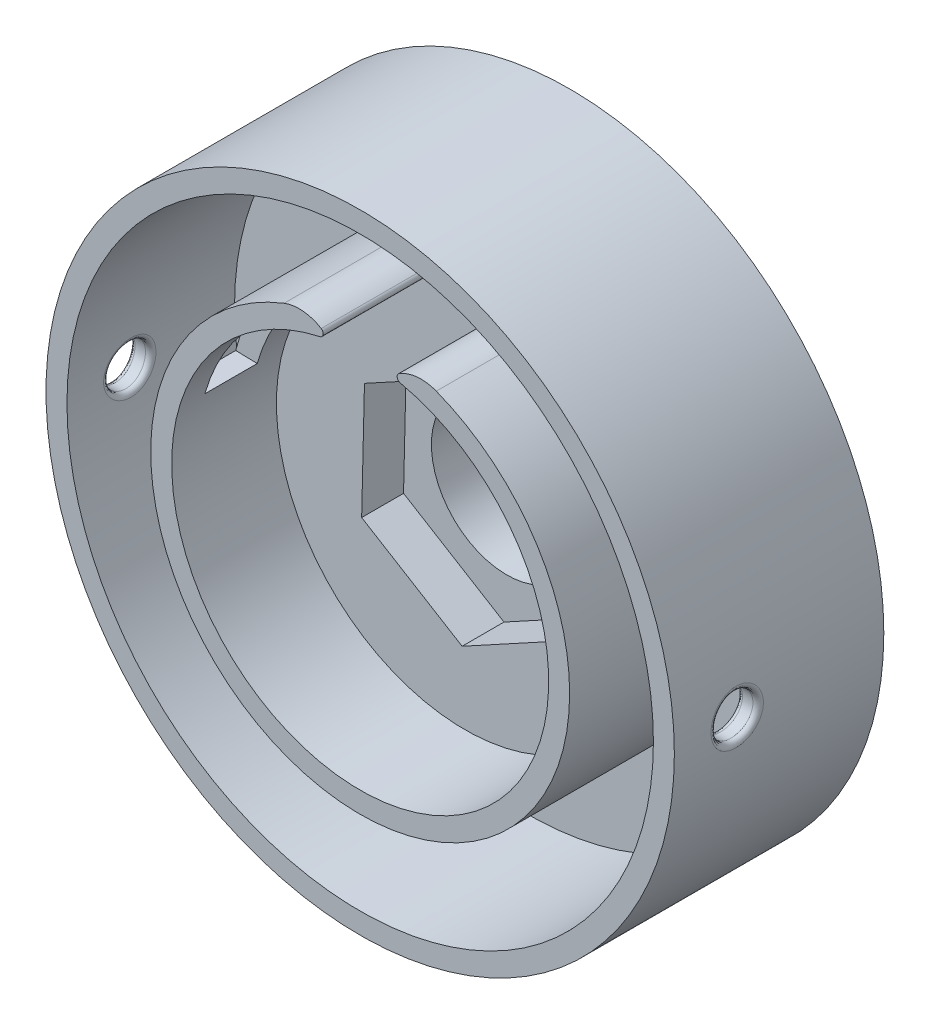
SolidWorks part; units mm, degrees
ref_plane "Front Plane" through (0, 0, 0) normal (0, 0, 1) x (1, 0, 0)
ref_plane "Top Plane" through (0, 0, 0) normal (0, 1, 0) x (1, 0, 0)
ref_plane "Right Plane" through (0, 0, 0) normal (1, 0, 0) x (0, 0, -1)
sketch "Sketch1" plane through (0, 0, 0) normal (0, 0, 1) x (1, 0, 0)
  circle A0 centre (0, 0) radius 15
extrude "Boss-Extrude1" add sketch "Sketch1" along normal blind 10
sketch "Sketch2" plane through (0, 0, 10) normal (0, 0, 1) x (1, 0, 0)
  circle A0 centre (0, 0) radius 3.6
extrude "Cut-Extrude1" cut sketch "Sketch2" against normal through all
sketch "Sketch3" plane through (0, 0, 10) normal (0, 0, 1) x (1, 0, 0)
  circle A0 centre (0, 0) radius 9
extrude "Cut-Extrude2" cut sketch "Sketch3" against normal blind 5
sketch "Sketch4" plane through (0, 0, 5) normal (0, 0, 1) x (1, 0, 0)
  line L1 (4.7958, -2.9234) -> (4.9296, 2.6916)
  line L2 (4.9296, 2.6916) -> (0.1338, 5.615)
  line L3 (0.1338, 5.615) -> (-4.7958, 2.9234)
  line L4 (-4.7958, 2.9234) -> (-4.9296, -2.6916)
  line L5 (-4.9296, -2.6916) -> (-0.1338, -5.615)
  line L6 (-0.1338, -5.615) -> (4.7958, -2.9234)
  circle A0 centre (0, 0) radius 4.8641 construction
  dimension "D1" = 11.23
extrude "Cut-Extrude3" cut sketch "Sketch4" against normal blind 2
sketch "Sketch5" plane through (0, 0, 10) normal (0, 0, 1) x (1, 0, 0)
  circle A0 centre (0, 0) radius 10
  circle A1 centre (0, 0) radius 14
extrude "Cut-Extrude4" cut sketch "Sketch5" against normal blind 8
sketch "Sketch6" plane through (0, 0, 10) normal (0, 0, 1) x (1, 0, 0)
  circle A0 centre (0, 0) radius 15
  circle A1 centre (0, 0) radius 14.5
sketch "Sketch7" plane through (0, 0, 10) normal (0, 0, 1) x (1, 0, 0)
  line L1 (-1.5, 12.2356) -> (1.5, 12.2356)
  line L2 (-1.5, 12.2356) -> (-1.5, 8.8741)
  line L3 (-1.5, 8.8741) -> (1.5, 8.8741)
  line L4 (1.5, 12.2356) -> (1.5, 8.8741)
  circle A0 centre (0, 0) radius 9 construction
  dimension "D1" = 3
  dimension "D2" = 1.5
extrude "Cut-Extrude6" cut sketch "Sketch7" against normal blind 5
fillet "Fillet2" radius 2 2 edges at (-1.5, 9.8869, 7.5) (1.5, 9.8869, 7.5)
fillet "Fillet3" radius 0.2 2 edges at (1.5, 8.8741, 7.5) (-1.5, 8.8741, 7.5)
sketch "Sketch8" plane through (0, 0, 0) normal (0, 0, -1) x (-1, 0, 0)
  line L1 (-2.2, -5.95) -> (2.2, -5.95)
  line L2 (-2.2, -5.95) -> (-2.2, -8.35)
  line L3 (-2.2, -8.35) -> (2.2, -8.35)
  line L4 (2.2, -5.95) -> (2.2, -8.35)
  dimension "D1" = 2.2
  dimension "D2" = 5.95
  dimension "D3" = 2.4
  dimension "D4" = 4.4
extrude "Cut-Extrude7" cut sketch "Sketch8" against normal blind 3
sketch "Sketch9" plane through (4.8627, -0.1159, 0) normal (-0.9997, 0.0238, 0) x (0, 0, 1)
  line L0 (10, -10) -> (10, 9.4002) construction
  line L1 (6.25, 6.2271) -> (8.75, 6.2271)
  line L2 (6.25, 6.2271) -> (6.25, 2.2271)
  line L3 (6.25, 2.2271) -> (8.75, 2.2271)
  line L4 (8.75, 6.2271) -> (8.75, 2.2271)
  line L5 (10, 9.2271) -> (5, 9.2271) construction
  dimension "D1" = 1.25
  dimension "D2" = 3
  dimension "D3" = 2.5
  dimension "D4" = 4
extrude "Cut-Extrude8" cut sketch "Sketch9" along normal blind 15
ref_plane "Plane1" through (15, 0, 0) normal (1, 0, 0) x (0, 0, -1)
sketch "Sketch10" plane through (15, 0, 0) normal (1, 0, 0) x (0, 0, -1)
  line L0 (0, 15) -> (-10, 15) construction
  line L1 (0, -15) -> (0, 15) construction
  circle A0 centre (-7, 0) radius 1
  dimension "D1" = 15
  dimension "D2" = 7
extrude "Cut-Extrude9" cut sketch "Sketch10" against normal up to next
fillet "Fillet6" radius 0.25 2 edges at (14.9983, -0.2275, 7.9738) (13.9982, 0.2271, 7.9739)
ref_plane "Plane2" through (-15, 0, 0) normal (1, 0, 0) x (0, 0, -1)
sketch "Sketch12" plane through (-15, 0, 0) normal (1, 0, 0) x (0, 0, -1)
  line L0 (0, -15) -> (0, 15) construction
  line L1 (0, 15) -> (-10, 15) construction
  circle A0 centre (-7, 0) radius 1
  dimension "D1" = 7
  dimension "D2" = 15
extrude "Cut-Extrude11" cut sketch "Sketch12" along normal up to next
fillet "Fillet7" radius 0.25 2 edges at (-13.9982, -0.2271, 6.0261) (-14.9983, 0.2275, 6.0262)
